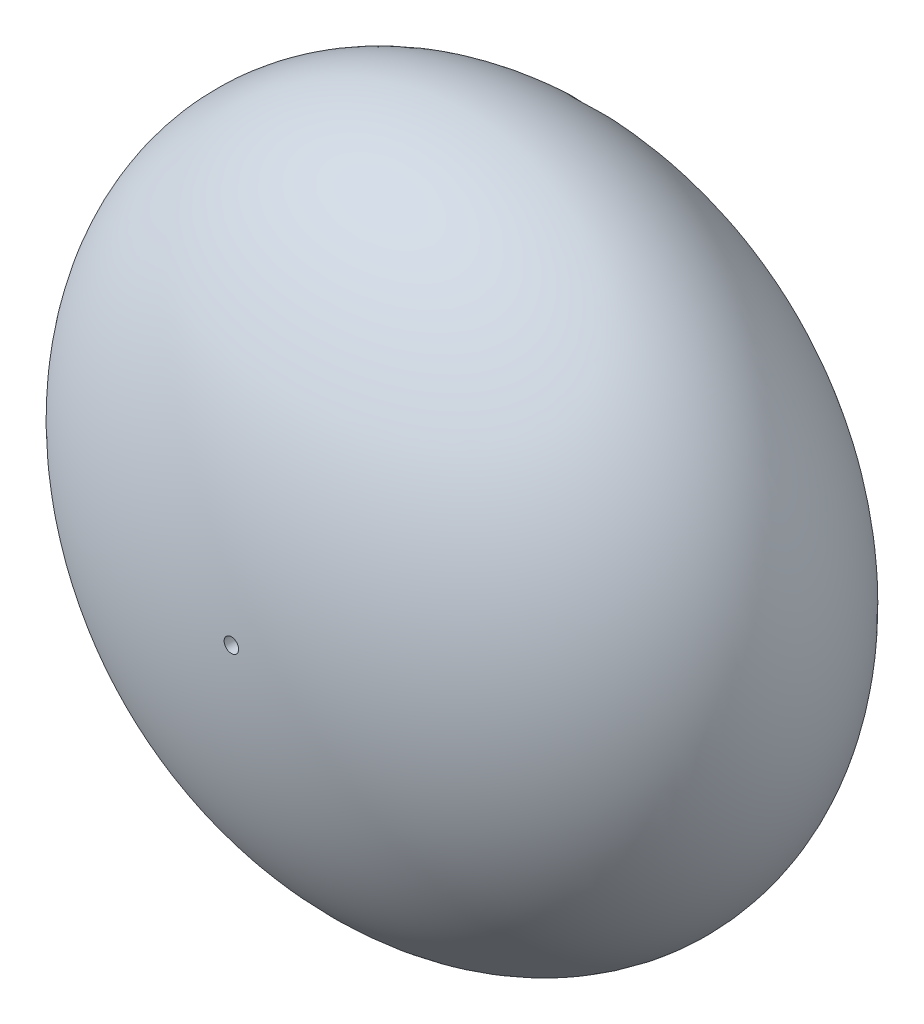
SolidWorks part; units mm, degrees
ref_plane "Front Plane" through (0, 0, 0) normal (0, 0, 1) x (1, 0, 0)
ref_plane "Top Plane" through (0, 0, 0) normal (0, 1, 0) x (1, 0, 0)
ref_plane "Right Plane" through (0, 0, 0) normal (1, 0, 0) x (0, 0, -1)
other "Center of Mass"
sketch "Sketch1" plane through (0, 0, 0) normal (0, 1, 0) x (1, 0, 0)
  line L0 (0, 17.5) -> (0, -17.5) construction
  line L1 (0, 17.5) -> (0, -17.5)
  ellipse E0 centre (0, 0) end of major axis (-26.25, 0) minor radius 17.5 (0, -17.5) -> (0, 17.5) ccw
  dimension "D1" = 17.5
  dimension "D2" = 26.25
revolve "Revolve4" add sketch "Sketch1" angle 360 about L0
sketch "Sketch3" plane through (0, 0, 0) normal (0, 0, 1) x (1, 0, 0)
  circle A0 centre (0, 0) radius 7
  dimension "D1" = 14
extrude "Cut-Extrude1" cut sketch "Sketch3" along normal blind 13
sketch "Sketch4" plane through (0, 0, 0) normal (0, 0, 1) x (1, 0, 0)
  circle A0 centre (0, 0) radius 0.55
  dimension "D1" = 1.1
extrude "Cut-Extrude2" cut sketch "Sketch4" against normal through all both and the other way through all
sketch "Sketch5" plane through (0, 0, 0) normal (0, 1, 0) x (1, 0, 0)
  circle A0 centre (0, 10) radius 1.4
  dimension "D1" = 2.8
  dimension "D2" = 10
extrude "Cut-Extrude3" cut sketch "Sketch5" against normal through all both and the other way through all
